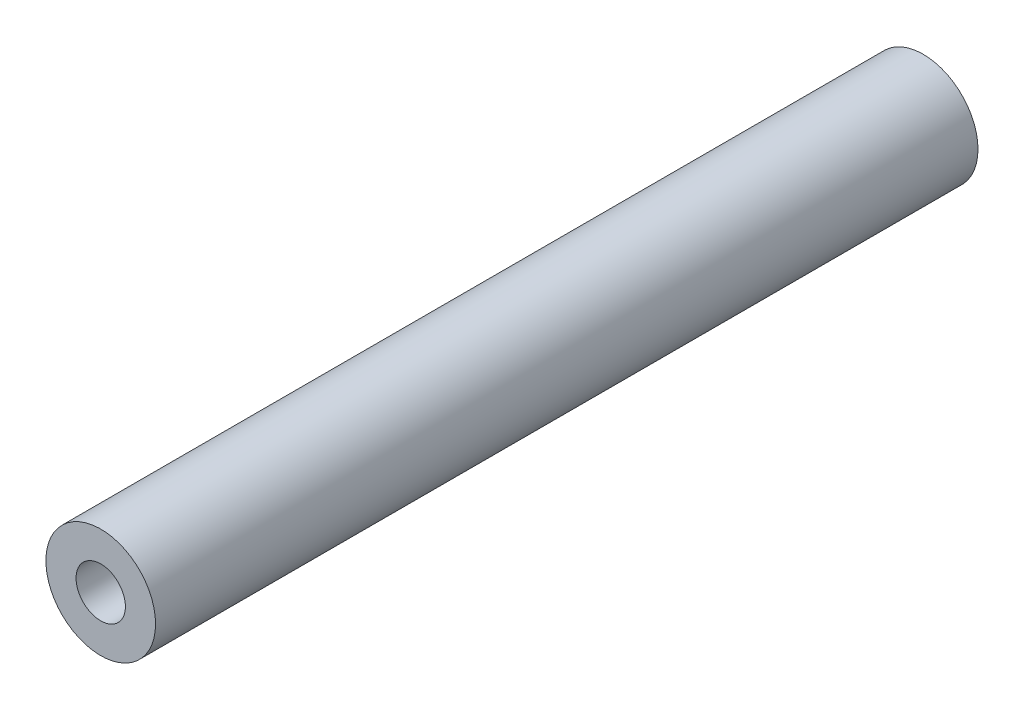
SolidWorks part; units mm, degrees
ref_plane "Front Plane" through (0, 0, 0) normal (0, 0, 1) x (1, 0, 0)
ref_plane "Top Plane" through (0, 0, 0) normal (0, 1, 0) x (1, 0, 0)
ref_plane "Right Plane" through (0, 0, 0) normal (1, 0, 0) x (0, 0, -1)
sketch "Sketch1" plane through (0, 0, 0) normal (0, 0, 1) x (1, 0, 0)
  circle A0 centre (0, 0) radius 5
  dimension "D1" = 10
extrude "Boss-Extrude1" add sketch "Sketch1" along normal blind 75
sketch "Sketch2" plane through (0, 0, 75) normal (0, 0, 1) x (1, 0, 0)
  circle A0 centre (0, 0) radius 2.25
  dimension "D1" = 4.5
extrude "Cut-Extrude1" cut sketch "Sketch2" against normal blind 12
